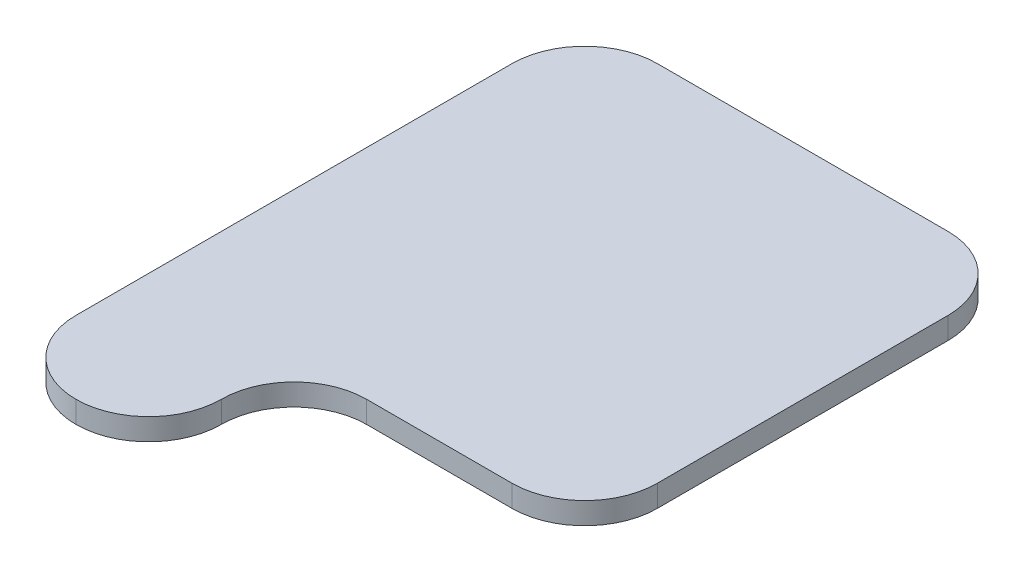
SolidWorks part; units mm, degrees
ref_plane "Front Plane" through (0, 0, 0) normal (0, 0, 1) x (1, 0, 0)
ref_plane "Top Plane" through (0, 0, 0) normal (0, 1, 0) x (1, 0, 0)
ref_plane "Right Plane" through (0, 0, 0) normal (1, 0, 0) x (0, 0, -1)
sketch "Sketch1" plane through (0, 0, 0) normal (0, 1, 0) x (1, 0, 0)
  line L1 (0, 0) -> (300, 0)
  line L2 (0, 0) -> (0, 300)
  line L3 (0, 300) -> (300, 300)
  line L4 (300, 0) -> (300, 300)
  line L5 (0, 0) -> (100, 0)
  line L6 (0, 0) -> (0, -100)
  line L7 (0, -100) -> (100, -100)
  line L8 (100, 0) -> (100, -100)
  dimension "D1" = 300
  dimension "D2" = 300
  dimension "D3" = 100
  dimension "D4" = 100
extrude "Boss-Extrude1" add sketch "Sketch1" along normal blind 15 contours L1 L4 L3 L2 | L8 L1 L6 L7 region at (150, 0, -150) region at (50, 0, 50)
fillet "Fillet1" radius 50 6 edges at (0, 7.5, -300) (0, 7.5, 100) (300, 7.5, -300) (300, 7.5, 0) (100, 7.5, 100) (100, 7.5, 0)
